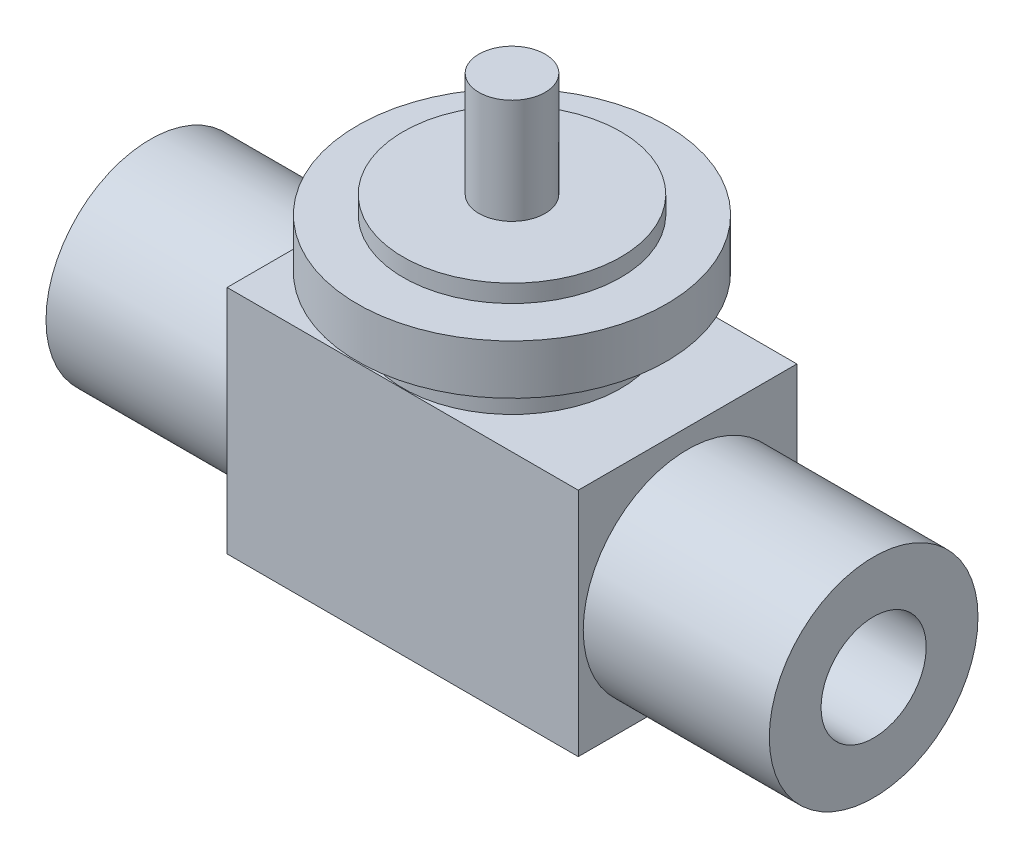
SolidWorks part; units mm, degrees
ref_plane "Front Plane" through (0, 0, 0) normal (0, 0, 1) x (1, 0, 0)
ref_plane "Top Plane" through (0, 0, 0) normal (0, 1, 0) x (1, 0, 0)
ref_plane "Right Plane" through (0, 0, 0) normal (1, 0, 0) x (0, 0, -1)
sketch "Body Sketch" plane through (0, 0, 0) normal (0, 0, 1) x (1, 0, 0)
  line L0 (-15.9, -9.7) -> (15.9, -9.7)
  line L1 (15.9, -9.7) -> (15.9, 11.2)
  line L2 (15.9, 11.2) -> (-15.9, 11.2)
  line L3 (-15.9, 11.2) -> (-15.9, -9.7)
extrude "Body" add sketch "Body Sketch" along normal mid plane 19.8
ref_axis "Engine Axis" through (36.025, 0, 0) along (-1, 0, 0)
ref_axis "Stem Axis" through (0, -11.735, 0) along (0, 1, 0)
sketch "Nut +X Sketch" plane through (0, 0, 0) normal (0, 0, 1) x (1, 0, 0)
  line L0 (-1000, 0) -> (1000, 0) construction
  line L1 (15.9, 0) -> (32.75, 0)
  line L2 (32.75, 0) -> (32.75, 9.45)
  line L3 (32.75, 9.45) -> (15.9, 9.45)
  line L4 (15.9, 9.45) -> (15.9, 0)
revolve "Nut +X" add sketch "Nut +X Sketch" angle 360 about L0
sketch "Nut -X Sketch" plane through (0, 0, 0) normal (0, 0, 1) x (1, 0, 0)
  line L0 (-1000, 0) -> (1000, 0) construction
  line L1 (-32.75, 0) -> (-15.9, 0)
  line L2 (-15.9, 0) -> (-15.9, 9.45)
  line L3 (-15.9, 9.45) -> (-32.75, 9.45)
  line L4 (-32.75, 9.45) -> (-32.75, 0)
revolve "Nut -X" add sketch "Nut -X Sketch" angle 360 about L0
sketch "Socket +X Sketch" plane through (0, 0, 0) normal (0, 0, 1) x (1, 0, 0)
  line L0 (-1000, 0) -> (1000, 0) construction
  line L1 (15.95, 0) -> (33.75, 0)
  line L2 (33.75, 0) -> (33.75, 4.7625)
  line L3 (33.75, 4.7625) -> (15.95, 4.7625)
  line L4 (15.95, 4.7625) -> (15.95, 0)
revolve "Socket +X" cut sketch "Socket +X Sketch" angle 360 about L0
sketch "Socket -X Sketch" plane through (0, 0, 0) normal (0, 0, 1) x (1, 0, 0)
  line L0 (-1000, 0) -> (1000, 0) construction
  line L1 (-33.75, 0) -> (-15.95, 0)
  line L2 (-15.95, 0) -> (-15.95, 4.7625)
  line L3 (-15.95, 4.7625) -> (-33.75, 4.7625)
  line L4 (-33.75, 4.7625) -> (-33.75, 0)
revolve "Socket -X" cut sketch "Socket -X Sketch" angle 360 about L0
sketch "Stem Sketch" plane through (0, 0, 0) normal (0, 0, 1) x (1, 0, 0)
  line L0 (0, -500) -> (0, 500) construction
  line L1 (0, 11.2) -> (9.85, 11.2)
  line L2 (9.85, 11.2) -> (9.85, 15.4)
  line L3 (9.85, 15.4) -> (14, 15.4)
  line L4 (14, 15.4) -> (14, 19.9)
  line L5 (14, 19.9) -> (9.85, 19.9)
  line L6 (9.85, 19.9) -> (9.85, 21.5)
  line L7 (9.85, 21.5) -> (3, 21.5)
  line L8 (3, 21.5) -> (3, 31)
  line L9 (3, 31) -> (0, 31)
  line L10 (0, 31) -> (0, 11.2)
revolve "Stem" add sketch "Stem Sketch" angle 360 about L0
